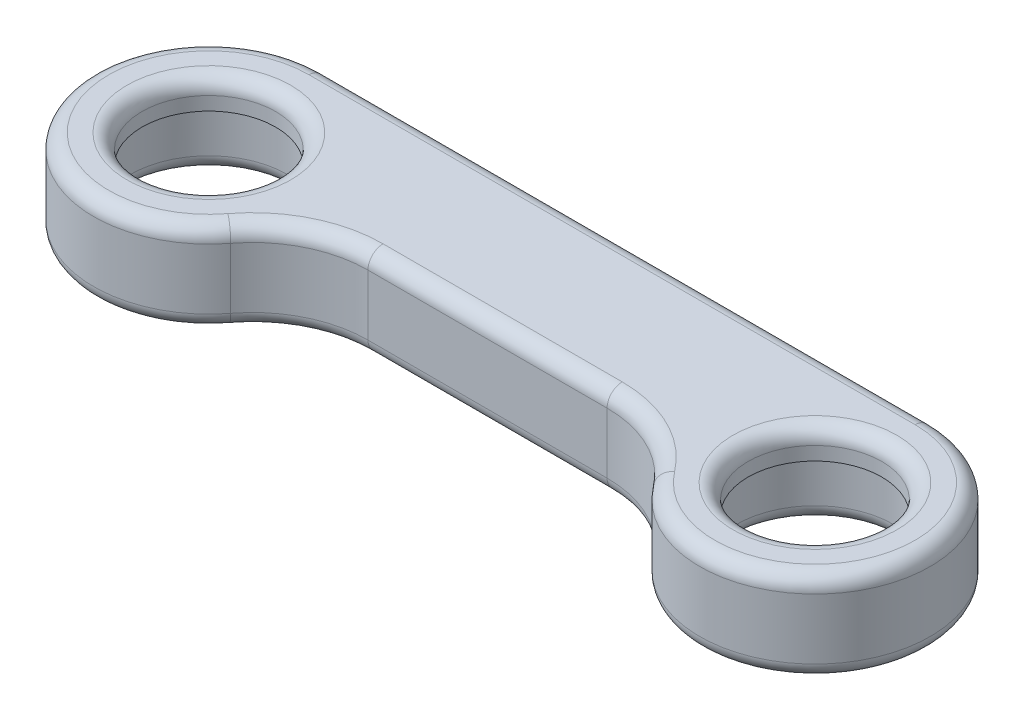
SolidWorks part; units mm, degrees
ref_plane "Front Plane" through (0, 0, 0) normal (0, 0, 1) x (1, 0, 0)
ref_plane "Top Plane" through (0, 0, 0) normal (0, 1, 0) x (1, 0, 0)
ref_plane "Right Plane" through (0, 0, 0) normal (1, 0, 0) x (0, 0, -1)
sketch "Sketch1" plane through (0, 0, 0) normal (0, 1, 0) x (1, 0, 0)
  line L2 (-15.875, 0) -> (15.875, 0) construction
  line L4 (-15.875, 6.04) -> (15.875, 6.04)
  line L8 (-15.875, -6.04) -> (15.875, -6.04)
  arc A12 (-15.875, -6.04) -> (-15.875, 6.04) centre (-15.875, 0) cw
  arc A18 (15.875, -6.04) -> (15.875, 6.04) centre (15.875, 0) ccw
  circle A22 centre (-15.875, 0) radius 4.125
  circle A23 centre (15.875, 0) radius 4.125
  point P1 (0, 0)
  dimension "D5" = 8.25
  dimension "D2" = 31.75
  dimension "D3" = 12.08
extrude "Boss-Extrude1" add sketch "Sketch1" along normal blind 4.5
sketch "Sketch2" plane through (0, 4.5, 0) normal (0, 1, 0) x (1, 0, 0)
  line L28 (-15.875, -6.04) -> (15.875, -6.04)
  line L29 (15.875, 6.04) -> (-15.875, 6.04)
  line L30 (-15.875, -6.04) -> (15.875, -6.04)
  line L31 (15.875, 6.04) -> (-15.875, 6.04)
  circle A2 centre (15.875, 0) radius 4.125 construction
  circle A4 centre (-15.875, 0) radius 4.125 construction
  arc A5 (-15.875, 6.04) -> (-15.875, -6.04) centre (-15.875, 0) ccw
  arc A7 (15.875, -6.04) -> (15.875, 6.04) centre (15.875, 0) ccw
  arc A8 (-15.875, 6.04) -> (-15.875, -6.04) centre (-15.875, 0) ccw
  arc A9 (15.875, -6.04) -> (15.875, 6.04) centre (15.875, 0) ccw
  circle A10 centre (15.875, 0) radius 4.125 construction
  circle A11 centre (-15.875, 0) radius 4.125 construction
  circle A12 centre (-15.875, 0) radius 3.5
  circle A13 centre (15.875, 0) radius 3.5
  dimension "D2" = 7
  dimension "D1" = 0
extrude "Boss-Extrude2" add sketch "Sketch2" along normal offset from surface (1.5 mm away) 6 up to face at (-15.875, 0, 4.125)
sketch "Sketch3" plane through (0, 0, 0) normal (0, -1, 0) x (1, 0, 0)
  line L6 (15.875, 6.04) -> (-15.875, 6.04)
  line L7 (-15.875, -6.04) -> (15.875, -6.04)
  line L10 (15.875, 6.04) -> (-15.875, 6.04)
  line L11 (-15.875, -6.04) -> (15.875, -6.04)
  arc A2 (15.875, -6.04) -> (15.875, 6.04) centre (15.875, 0) ccw
  arc A3 (15.875, -6.04) -> (15.875, 6.04) centre (15.875, 0) ccw
  arc A11 (-15.875, 6.04) -> (-15.875, -6.04) centre (-15.875, 0) ccw
  arc A17 (-15.875, 6.04) -> (-15.875, -6.04) centre (-15.875, 0) ccw
  dimension "D1" = 0
extrude "Cut-Extrude1" cut sketch "Sketch3" against normal offset from surface (1.2375 mm away) 4.7625 up to face at (15.875, 6, -3.5)
sketch "Sketch4" plane through (0, 6, 0) normal (0, 1, 0) x (1, 0, 0)
  line L0 (15.875, -6.04) -> (-15.875, -6.04) construction
  line L1 (-6.2635, -1.2775) -> (6.2635, -1.2775)
  line L2 (-15.875, -6.04) -> (15.875, -6.04)
  arc A0 (-15.875, -6.04) -> (-11.0693, -3.6587) centre (-15.875, 0) ccw
  arc A1 (15.875, -6.04) -> (11.0693, -3.6587) centre (15.875, 0) cw
  arc A2 (15.875, -6.04) -> (15.875, 6.04) centre (15.875, 0) ccw construction
  arc A3 (11.0693, -3.6587) -> (6.2635, -1.2775) centre (6.2635, -7.3175) ccw
  arc A4 (-11.0693, -3.6587) -> (-6.2635, -1.2775) centre (-6.2635, -7.3175) cw
  dimension "D1" = 4.7625
extrude "Cut-Extrude2" cut sketch "Sketch4" against normal through all
fillet "Fillet2" radius 0.7937 8 edges at (0, 1.2375, -6.04) (-21.287, 1.2375, 2.6817) (21.287, 1.2375, 2.6817) (15.875, 1.2375, -4.125) (-15.875, 1.2375, -4.125) (0, 1.2375, 1.2775) (8.9452, 1.2375, 1.9055) (-8.9452, 1.2375, 1.9055)
fillet "Fillet3" radius 0.7937 8 edges at (-21.287, 6, 2.6817) (0, 6, -6.04) (21.287, 6, 2.6817) (-15.875, 6, -3.5) (15.875, 6, -3.5) (8.9452, 6, 1.9055) (0, 6, 1.2775) (-8.9452, 6, 1.9055)
